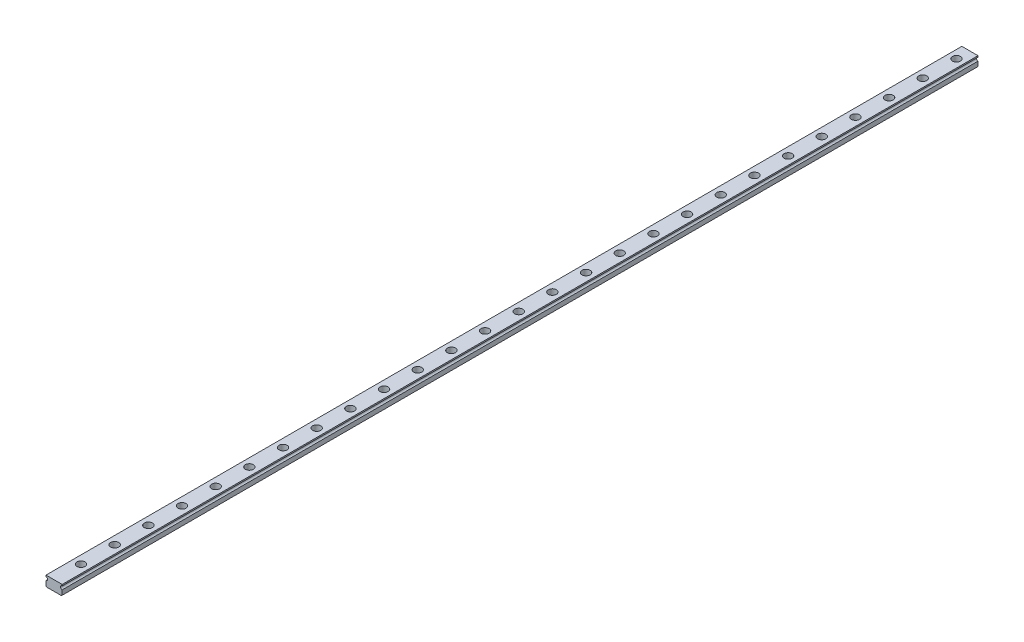
SolidWorks part; units mm, degrees
ref_plane "前视基准面" through (0, 0, 0) normal (0, 0, 1) x (1, 0, 0)
ref_plane "上视基准面" through (0, 0, 0) normal (0, 1, 0) x (1, 0, 0)
ref_plane "右视基准面" through (0, 0, 0) normal (1, 0, 0) x (0, 0, -1)
sketch "草图1" plane through (0, 0, 0) normal (0, 0, 1) x (1, 0, 0)
  line L0 (-6, 7.5) -> (-6, 6.5)
  line L1 (-6, 4) -> (-6, 0.5)
  line L2 (-6, 0.5) -> (-5.5, 0)
  line L3 (-5.5, 0) -> (5.5, 0)
  line L4 (5.5, 0) -> (6, 0.5)
  line L5 (6, 0.5) -> (6, 4)
  line L6 (6, 6.5) -> (6, 7.5)
  line L7 (6, 7.5) -> (-6, 7.5)
  arc A0 (-6, 6.5) -> (-6, 4) centre (-6, 5.25) cw
  arc A1 (6, 4) -> (6, 6.5) centre (6, 5.25) cw
extrude "凸台-拉伸1" add sketch "草图1" along normal blind 680
sketch "草图2" plane through (0, 0, 0) normal (1, 0, 0) x (0, 0, -1)
  line L0 (-10, 7.5) -> (-7, 7.5)
  line L1 (-7, 7.5) -> (-7, 3)
  line L2 (-7, 3) -> (-8.25, 3)
  line L3 (-8.25, 3) -> (-8.25, 0)
  line L4 (-8.25, 0) -> (-10, 0)
  line L5 (-10, 0) -> (-10, 7.5)
  line L6 (-10, 0) -> (-10, 7.5) construction
revolve "切除-旋转1" cut sketch "草图2" angle 360 about L6 reverse direction yes
ref_plane "基准面4" through (0, 7.5, 0) normal (0, 1, 0) x (1, 0, 0)
ref_plane "基准面5" through (0, 0, 0) normal (1, 0, 0) x (0, 0, -1)
ref_plane "基准面6" through (0, 0, 0) normal (1, 0, 0) x (0, 0, -1)
ref_plane "基准面7" through (0, 0, 0) normal (1, 0, 0) x (0, 0, -1)
ref_plane "基准面8" through (0, 0, 0) normal (1, 0, 0) x (0, 0, -1)
ref_plane "基准面9" through (0, 0, 0) normal (1, 0, 0) x (0, 0, -1)
ref_plane "基准面10" through (0, 0, 0) normal (1, 0, 0) x (0, 0, -1)
ref_plane "基准面11" through (0, 0, 0) normal (1, 0, 0) x (0, 0, -1)
ref_plane "基准面12" through (0, 0, 0) normal (1, 0, 0) x (0, 0, -1)
ref_plane "基准面13" through (0, 0, 0) normal (1, 0, 0) x (0, 0, -1)
ref_plane "基准面14" through (0, 0, 0) normal (1, 0, 0) x (0, 0, -1)
ref_plane "基准面15" through (0, 0, 0) normal (1, 0, 0) x (0, 0, -1)
ref_plane "基准面16" through (0, 0, 0) normal (1, 0, 0) x (0, 0, -1)
sketch "草图3" plane through (0, 0, 0) normal (1, 0, 0) x (0, 0, -1)
  line L0 (-310, 7.5) -> (-307, 7.5)
  line L1 (-307, 7.5) -> (-307, 3)
  line L2 (-307, 3) -> (-308.25, 3)
  line L3 (-308.25, 3) -> (-308.25, 0)
  line L4 (-308.25, 0) -> (-310, 0)
  line L5 (-310, 0) -> (-310, 7.5)
  line L6 (-310, 0) -> (-310, 7.5) construction
sketch "草图4" plane through (0, 0, 0) normal (1, 0, 0) x (0, 0, -1)
  line L0 (-285, 7.5) -> (-282, 7.5)
  line L1 (-282, 7.5) -> (-282, 3)
  line L2 (-282, 3) -> (-283.25, 3)
  line L3 (-283.25, 3) -> (-283.25, 0)
  line L4 (-283.25, 0) -> (-285, 0)
  line L5 (-285, 0) -> (-285, 7.5)
  line L6 (-285, 0) -> (-285, 7.5) construction
sketch "草图5" plane through (0, 0, 0) normal (1, 0, 0) x (0, 0, -1)
  line L0 (-260, 7.5) -> (-257, 7.5)
  line L1 (-257, 7.5) -> (-257, 3)
  line L2 (-257, 3) -> (-258.25, 3)
  line L3 (-258.25, 3) -> (-258.25, 0)
  line L4 (-258.25, 0) -> (-260, 0)
  line L5 (-260, 0) -> (-260, 7.5)
  line L6 (-260, 0) -> (-260, 7.5) construction
sketch "草图6" plane through (0, 0, 0) normal (1, 0, 0) x (0, 0, -1)
  line L0 (-235, 7.5) -> (-232, 7.5)
  line L1 (-232, 7.5) -> (-232, 3)
  line L2 (-232, 3) -> (-233.25, 3)
  line L3 (-233.25, 3) -> (-233.25, 0)
  line L4 (-233.25, 0) -> (-235, 0)
  line L5 (-235, 0) -> (-235, 7.5)
  line L6 (-235, 0) -> (-235, 7.5) construction
sketch "草图7" plane through (0, 0, 0) normal (1, 0, 0) x (0, 0, -1)
  line L0 (-210, 7.5) -> (-207, 7.5)
  line L1 (-207, 7.5) -> (-207, 3)
  line L2 (-207, 3) -> (-208.25, 3)
  line L3 (-208.25, 3) -> (-208.25, 0)
  line L4 (-208.25, 0) -> (-210, 0)
  line L5 (-210, 0) -> (-210, 7.5)
  line L6 (-210, 0) -> (-210, 7.5) construction
sketch "草图8" plane through (0, 0, 0) normal (1, 0, 0) x (0, 0, -1)
  line L0 (-185, 7.5) -> (-182, 7.5)
  line L1 (-182, 7.5) -> (-182, 3)
  line L2 (-182, 3) -> (-183.25, 3)
  line L3 (-183.25, 3) -> (-183.25, 0)
  line L4 (-183.25, 0) -> (-185, 0)
  line L5 (-185, 0) -> (-185, 7.5)
  line L6 (-185, 0) -> (-185, 7.5) construction
sketch "草图9" plane through (0, 0, 0) normal (1, 0, 0) x (0, 0, -1)
  line L0 (-160, 7.5) -> (-157, 7.5)
  line L1 (-157, 7.5) -> (-157, 3)
  line L2 (-157, 3) -> (-158.25, 3)
  line L3 (-158.25, 3) -> (-158.25, 0)
  line L4 (-158.25, 0) -> (-160, 0)
  line L5 (-160, 0) -> (-160, 7.5)
  line L6 (-160, 0) -> (-160, 7.5) construction
sketch "草图10" plane through (0, 0, 0) normal (1, 0, 0) x (0, 0, -1)
  line L0 (-135, 7.5) -> (-132, 7.5)
  line L1 (-132, 7.5) -> (-132, 3)
  line L2 (-132, 3) -> (-133.25, 3)
  line L3 (-133.25, 3) -> (-133.25, 0)
  line L4 (-133.25, 0) -> (-135, 0)
  line L5 (-135, 0) -> (-135, 7.5)
  line L6 (-135, 0) -> (-135, 7.5) construction
sketch "草图11" plane through (0, 0, 0) normal (1, 0, 0) x (0, 0, -1)
  line L0 (-110, 7.5) -> (-107, 7.5)
  line L1 (-107, 7.5) -> (-107, 3)
  line L2 (-107, 3) -> (-108.25, 3)
  line L3 (-108.25, 3) -> (-108.25, 0)
  line L4 (-108.25, 0) -> (-110, 0)
  line L5 (-110, 0) -> (-110, 7.5)
  line L6 (-110, 0) -> (-110, 7.5) construction
sketch "草图12" plane through (0, 0, 0) normal (1, 0, 0) x (0, 0, -1)
  line L0 (-85, 7.5) -> (-82, 7.5)
  line L1 (-82, 7.5) -> (-82, 3)
  line L2 (-82, 3) -> (-83.25, 3)
  line L3 (-83.25, 3) -> (-83.25, 0)
  line L4 (-83.25, 0) -> (-85, 0)
  line L5 (-85, 0) -> (-85, 7.5)
  line L6 (-85, 0) -> (-85, 7.5) construction
sketch "草图13" plane through (0, 0, 0) normal (1, 0, 0) x (0, 0, -1)
  line L0 (-60, 7.5) -> (-57, 7.5)
  line L1 (-57, 7.5) -> (-57, 3)
  line L2 (-57, 3) -> (-58.25, 3)
  line L3 (-58.25, 3) -> (-58.25, 0)
  line L4 (-58.25, 0) -> (-60, 0)
  line L5 (-60, 0) -> (-60, 7.5)
  line L6 (-60, 0) -> (-60, 7.5) construction
sketch "草图14" plane through (0, 0, 0) normal (1, 0, 0) x (0, 0, -1)
  line L0 (-35, 7.5) -> (-32, 7.5)
  line L1 (-32, 7.5) -> (-32, 3)
  line L2 (-32, 3) -> (-33.25, 3)
  line L3 (-33.25, 3) -> (-33.25, 0)
  line L4 (-33.25, 0) -> (-35, 0)
  line L5 (-35, 0) -> (-35, 7.5)
  line L6 (-35, 0) -> (-35, 7.5) construction
revolve "切除-旋转2" cut sketch "草图3" angle 360 about L6 reverse direction yes
revolve "切除-旋转3" cut sketch "草图4" angle 360 about L6 reverse direction yes
revolve "切除-旋转4" cut sketch "草图5" angle 360 about L6 reverse direction yes
revolve "切除-旋转5" cut sketch "草图6" angle 360 about L6 reverse direction yes
revolve "切除-旋转6" cut sketch "草图7" angle 360 about L6 reverse direction yes
revolve "切除-旋转7" cut sketch "草图8" angle 360 about L6 reverse direction yes
revolve "切除-旋转8" cut sketch "草图9" angle 360 about L6 reverse direction yes
revolve "切除-旋转9" cut sketch "草图10" angle 360 about L6 reverse direction yes
revolve "切除-旋转10" cut sketch "草图11" angle 360 about L6 reverse direction yes
revolve "切除-旋转11" cut sketch "草图12" angle 360 about L6 reverse direction yes
revolve "切除-旋转12" cut sketch "草图13" angle 360 about L6 reverse direction yes
revolve "切除-旋转13" cut sketch "草图14" angle 360 about L6 reverse direction yes
ref_plane "基准面17" through (0, 0, 160) normal (0, 0, 1) x (1, 0, 0)
ref_plane "基准面18" through (0, 0, 180.95) normal (0, 0, 1) x (1, 0, 0)
ref_plane "基准面19" through (0, 3, 0) normal (0, 1, 0) x (1, 0, 0)
ref_plane "to_block XY" through (0, 0, 160) normal (0, 0, 1) x (1, 0, 0)
ref_plane "to_block XZ" through (0, 7.5, 0) normal (0, -1, 0) x (-1, 0, 0)
ref_plane "to_block YZ" through (0, 0, 0) normal (1, 0, 0) x (0, 0, -1)
ref_axis "to_block X" through (-80.9, 7.5, 160) along (1, 0, 0)
ref_axis "to_block Y" through (0, -50, 160) along (0, 1, 0)
ref_axis "to_block Z" through (0, 7.5, 80.9) along (0, 0, -1)
sketch3d "to_block"
  point P0 (0, 7.5, 160)
ref_plane "to_block_2 XY" through (0, 0, 180.95) normal (0, 0, 1) x (1, 0, 0)
ref_plane "to_block_2 XZ" through (0, 7.5, 0) normal (0, -1, 0) x (-1, 0, 0)
ref_plane "to_block_2 YZ" through (0, 0, 0) normal (1, 0, 0) x (0, 0, -1)
ref_axis "to_block_2 X" through (-80.9, 7.5, 180.95) along (1, 0, 0)
ref_axis "to_block_2 Y" through (0, -50, 180.95) along (0, 1, 0)
ref_axis "to_block_2 Z" through (0, 7.5, 80.9) along (0, 0, -1)
sketch3d "to_block_2"
  point P0 (0, 7.5, 180.95)
ref_plane "to_kue XY" through (0, 0, 0) normal (0, 1, 0) x (1, 0, 0)
ref_plane "to_kue XZ" through (0, 0, 160) normal (0, 0, 1) x (1, 0, 0)
ref_plane "to_kue YZ" through (0, 0, 0) normal (1, 0, 0) x (0, 0, -1)
ref_axis "to_kue X" through (-80.9, 0, 160) along (1, 0, 0)
ref_axis "to_kue Y" through (0, 0, 50) along (0, 0, -1)
ref_axis "to_kue Z" through (0, 50, 160) along (0, -1, 0)
sketch3d "to_kue"
  point P0 (0, 0, 160)
ref_plane "rail_to bolt2 XY" through (0, 3, 0) normal (0, 1, 0) x (1, 0, 0)
ref_plane "rail_to bolt2 XZ" through (0, 0, 35) normal (0, 0, 1) x (1, 0, 0)
ref_plane "rail_to bolt2 YZ" through (0, 0, 0) normal (1, 0, 0) x (0, 0, -1)
ref_axis "rail_to bolt2 X" through (-80.9, 3, 35) along (1, 0, 0)
ref_axis "rail_to bolt2 Y" through (0, 3, 50) along (0, 0, -1)
ref_axis "rail_to bolt2 Z" through (0, 50, 35) along (0, -1, 0)
sketch3d "rail_to bolt2"
  point P0 (0, 3, 35)
ref_plane "rail_to_bolt7 XY" through (0, 3, 0) normal (0, 1, 0) x (1, 0, 0)
ref_plane "rail_to_bolt7 XZ" through (0, 0, 160) normal (0, 0, 1) x (1, 0, 0)
ref_plane "rail_to_bolt7 YZ" through (0, 0, 0) normal (1, 0, 0) x (0, 0, -1)
ref_axis "rail_to_bolt7 X" through (-80.9, 3, 160) along (1, 0, 0)
ref_axis "rail_to_bolt7 Y" through (0, 3, 50) along (0, 0, -1)
ref_axis "rail_to_bolt7 Z" through (0, 50, 160) along (0, -1, 0)
sketch3d "rail_to_bolt7"
  point P0 (0, 3, 160)
ref_plane "rail_to_bolt6 XY" through (0, 3, 0) normal (0, 1, 0) x (1, 0, 0)
ref_plane "rail_to_bolt6 XZ" through (0, 0, 135) normal (0, 0, 1) x (1, 0, 0)
ref_plane "rail_to_bolt6 YZ" through (0, 0, 0) normal (1, 0, 0) x (0, 0, -1)
ref_axis "rail_to_bolt6 X" through (-80.9, 3, 135) along (1, 0, 0)
ref_axis "rail_to_bolt6 Y" through (0, 3, 50) along (0, 0, -1)
ref_axis "rail_to_bolt6 Z" through (0, 50, 135) along (0, -1, 0)
sketch3d "rail_to_bolt6"
  point P0 (0, 3, 135)
ref_plane "rail_to_bolt5 XY" through (0, 3, 0) normal (0, 1, 0) x (1, 0, 0)
ref_plane "rail_to_bolt5 XZ" through (0, 0, 110) normal (0, 0, 1) x (1, 0, 0)
ref_plane "rail_to_bolt5 YZ" through (0, 0, 0) normal (1, 0, 0) x (0, 0, -1)
ref_axis "rail_to_bolt5 X" through (-80.9, 3, 110) along (1, 0, 0)
ref_axis "rail_to_bolt5 Y" through (0, 3, 50) along (0, 0, -1)
ref_axis "rail_to_bolt5 Z" through (0, 50, 110) along (0, -1, 0)
sketch3d "rail_to_bolt5"
  point P0 (0, 3, 110)
ref_plane "rail_to_bolt4 XY" through (0, 3, 0) normal (0, 1, 0) x (1, 0, 0)
ref_plane "rail_to_bolt4 XZ" through (0, 0, 85) normal (0, 0, 1) x (1, 0, 0)
ref_plane "rail_to_bolt4 YZ" through (0, 0, 0) normal (1, 0, 0) x (0, 0, -1)
ref_axis "rail_to_bolt4 X" through (-80.9, 3, 85) along (1, 0, 0)
ref_axis "rail_to_bolt4 Y" through (0, 3, 50) along (0, 0, -1)
ref_axis "rail_to_bolt4 Z" through (0, 50, 85) along (0, -1, 0)
sketch3d "rail_to_bolt4"
  point P0 (0, 3, 85)
ref_plane "rail_to_bolt3 XY" through (0, 3, 0) normal (0, 1, 0) x (1, 0, 0)
ref_plane "rail_to_bolt3 XZ" through (0, 0, 60) normal (0, 0, 1) x (1, 0, 0)
ref_plane "rail_to_bolt3 YZ" through (0, 0, 0) normal (1, 0, 0) x (0, 0, -1)
ref_axis "rail_to_bolt3 X" through (-80.9, 3, 60) along (1, 0, 0)
ref_axis "rail_to_bolt3 Y" through (0, 3, 50) along (0, 0, -1)
ref_axis "rail_to_bolt3 Z" through (0, 50, 60) along (0, -1, 0)
sketch3d "rail_to_bolt3"
  point P0 (0, 3, 60)
ref_plane "rail_to_bolt13 XY" through (0, 3, 0) normal (0, 1, 0) x (1, 0, 0)
ref_plane "rail_to_bolt13 XZ" through (0, 0, 310) normal (0, 0, 1) x (1, 0, 0)
ref_plane "rail_to_bolt13 YZ" through (0, 0, 0) normal (1, 0, 0) x (0, 0, -1)
ref_axis "rail_to_bolt13 X" through (-80.9, 3, 310) along (1, 0, 0)
ref_axis "rail_to_bolt13 Y" through (0, 3, 50) along (0, 0, -1)
ref_axis "rail_to_bolt13 Z" through (0, 50, 310) along (0, -1, 0)
sketch3d "rail_to_bolt13"
  point P0 (0, 3, 310)
ref_plane "rail_to_bolt12 XY" through (0, 3, 0) normal (0, 1, 0) x (1, 0, 0)
ref_plane "rail_to_bolt12 XZ" through (0, 0, 285) normal (0, 0, 1) x (1, 0, 0)
ref_plane "rail_to_bolt12 YZ" through (0, 0, 0) normal (1, 0, 0) x (0, 0, -1)
ref_axis "rail_to_bolt12 X" through (-80.9, 3, 285) along (1, 0, 0)
ref_axis "rail_to_bolt12 Y" through (0, 3, 50) along (0, 0, -1)
ref_axis "rail_to_bolt12 Z" through (0, 50, 285) along (0, -1, 0)
sketch3d "rail_to_bolt12"
  point P0 (0, 3, 285)
ref_plane "rail_to_bolt1 XY" through (0, 3, 0) normal (0, 1, 0) x (1, 0, 0)
ref_plane "rail_to_bolt1 XZ" through (0, 0, 10) normal (0, 0, 1) x (1, 0, 0)
ref_plane "rail_to_bolt1 YZ" through (0, 0, 0) normal (1, 0, 0) x (0, 0, -1)
ref_axis "rail_to_bolt1 X" through (-80.9, 3, 10) along (1, 0, 0)
ref_axis "rail_to_bolt1 Y" through (0, 3, 50) along (0, 0, -1)
ref_axis "rail_to_bolt1 Z" through (0, 50, 10) along (0, -1, 0)
sketch3d "rail_to_bolt1"
  point P0 (0, 3, 10)
ref_plane "rail_to_bolt11 XY" through (0, 3, 0) normal (0, 1, 0) x (1, 0, 0)
ref_plane "rail_to_bolt11 XZ" through (0, 0, 260) normal (0, 0, 1) x (1, 0, 0)
ref_plane "rail_to_bolt11 YZ" through (0.178, 0, 0) normal (1, 0, 0) x (0, 0, -1)
ref_axis "rail_to_bolt11 X" through (-80.9, 3, 260) along (1, 0, 0)
ref_axis "rail_to_bolt11 Y" through (0.178, 3, 50) along (0, 0, -1)
ref_axis "rail_to_bolt11 Z" through (0.178, 50, 260) along (0, -1, 0)
sketch3d "rail_to_bolt11"
  point P0 (0.178, 3, 260)
ref_plane "rail_to_bolt10 XY" through (0, 3, 0) normal (0, 1, 0) x (1, 0, 0)
ref_plane "rail_to_bolt10 XZ" through (0, 0, 235) normal (0, 0, 1) x (1, 0, 0)
ref_plane "rail_to_bolt10 YZ" through (0, 0, 0) normal (1, 0, 0) x (0, 0, -1)
ref_axis "rail_to_bolt10 X" through (-80.9, 3, 235) along (1, 0, 0)
ref_axis "rail_to_bolt10 Y" through (0, 3, 50) along (0, 0, -1)
ref_axis "rail_to_bolt10 Z" through (0, 50, 235) along (0, -1, 0)
sketch3d "rail_to_bolt10"
  point P0 (0, 3, 235)
ref_plane "rail_to_bolt9 XY" through (0, 3, 0) normal (0, 1, 0) x (1, 0, 0)
ref_plane "rail_to_bolt9 XZ" through (0, 0, 210) normal (0, 0, 1) x (1, 0, 0)
ref_plane "rail_to_bolt9 YZ" through (0, 0, 0) normal (1, 0, 0) x (0, 0, -1)
ref_axis "rail_to_bolt9 X" through (-80.9, 3, 210) along (1, 0, 0)
ref_axis "rail_to_bolt9 Y" through (0, 3, 50) along (0, 0, -1)
ref_axis "rail_to_bolt9 Z" through (0, 50, 210) along (0, -1, 0)
sketch3d "rail_to_bolt9"
  point P0 (0, 3, 210)
ref_plane "rail_to_bolt8 XY" through (0, 3, 0) normal (0, 1, 0) x (1, 0, 0)
ref_plane "rail_to_bolt8 XZ" through (0, 0, 185) normal (0, 0, 1) x (1, 0, 0)
ref_plane "rail_to_bolt8 YZ" through (0, 0, 0) normal (1, 0, 0) x (0, 0, -1)
ref_axis "rail_to_bolt8 X" through (-80.9, 3, 185) along (1, 0, 0)
ref_axis "rail_to_bolt8 Y" through (0, 3, 50) along (0, 0, -1)
ref_axis "rail_to_bolt8 Z" through (0, 50, 185) along (0, -1, 0)
sketch3d "rail_to_bolt8"
  point P0 (0, 3, 185)
ref_plane "rail_to_bolt 7 XY" through (0, 3, 0) normal (0, 1, 0) x (1, 0, 0)
ref_plane "rail_to_bolt 7 XZ" through (0, 0, 160) normal (0, 0, 1) x (1, 0, 0)
ref_plane "rail_to_bolt 7 YZ" through (0, 0, 0) normal (1, 0, 0) x (0, 0, -1)
ref_axis "rail_to_bolt 7 X" through (-80.9, 3, 160) along (1, 0, 0)
ref_axis "rail_to_bolt 7 Y" through (0, 3, 50) along (0, 0, -1)
ref_axis "rail_to_bolt 7 Z" through (0, 50, 160) along (0, -1, 0)
sketch3d "rail_to_bolt 7"
  point P0 (0, 3, 160)
ref_plane "rail_to_bolt 6 XY" through (0, 3, 0) normal (0, 1, 0) x (1, 0, 0)
ref_plane "rail_to_bolt 6 XZ" through (0, 0, 135) normal (0, 0, 1) x (1, 0, 0)
ref_plane "rail_to_bolt 6 YZ" through (0, 0, 0) normal (1, 0, 0) x (0, 0, -1)
ref_axis "rail_to_bolt 6 X" through (-80.9, 3, 135) along (1, 0, 0)
ref_axis "rail_to_bolt 6 Y" through (0, 3, 50) along (0, 0, -1)
ref_axis "rail_to_bolt 6 Z" through (0, 50, 135) along (0, -1, 0)
sketch3d "rail_to_bolt 6"
  point P0 (0, 3, 135)
ref_plane "rail_to_bolt 5 XY" through (0, 3, 0) normal (0, 1, 0) x (1, 0, 0)
ref_plane "rail_to_bolt 5 XZ" through (0, 0, 110) normal (0, 0, 1) x (1, 0, 0)
ref_plane "rail_to_bolt 5 YZ" through (0, 0, 0) normal (1, 0, 0) x (0, 0, -1)
ref_axis "rail_to_bolt 5 X" through (-80.9, 3, 110) along (1, 0, 0)
ref_axis "rail_to_bolt 5 Y" through (0, 3, 50) along (0, 0, -1)
ref_axis "rail_to_bolt 5 Z" through (0, 50, 110) along (0, -1, 0)
sketch3d "rail_to_bolt 5"
  point P0 (0, 3, 110)
ref_plane "rail_to_bolt 4 XY" through (0, 3, 0) normal (0, 1, 0) x (1, 0, 0)
ref_plane "rail_to_bolt 4 XZ" through (0, 0, 85) normal (0, 0, 1) x (1, 0, 0)
ref_plane "rail_to_bolt 4 YZ" through (0, 0, 0) normal (1, 0, 0) x (0, 0, -1)
ref_axis "rail_to_bolt 4 X" through (-80.9, 3, 85) along (1, 0, 0)
ref_axis "rail_to_bolt 4 Y" through (0, 3, 50) along (0, 0, -1)
ref_axis "rail_to_bolt 4 Z" through (0, 50, 85) along (0, -1, 0)
sketch3d "rail_to_bolt 4"
  point P0 (0, 3, 85)
ref_plane "rail_to_bolt 3 XY" through (0, 3, 0) normal (0, 1, 0) x (1, 0, 0)
ref_plane "rail_to_bolt 3 XZ" through (0, 0, 60) normal (0, 0, 1) x (1, 0, 0)
ref_plane "rail_to_bolt 3 YZ" through (0, 0, 0) normal (1, 0, 0) x (0, 0, -1)
ref_axis "rail_to_bolt 3 X" through (-80.9, 3, 60) along (1, 0, 0)
ref_axis "rail_to_bolt 3 Y" through (0, 3, 50) along (0, 0, -1)
ref_axis "rail_to_bolt 3 Z" through (0, 50, 60) along (0, -1, 0)
sketch3d "rail_to_bolt 3"
  point P0 (0, 3, 60)
ref_plane "rail_to_bolt 13 XY" through (0, 3, 0) normal (0, 1, 0) x (1, 0, 0)
ref_plane "rail_to_bolt 13 XZ" through (0, 0, 310) normal (0, 0, 1) x (1, 0, 0)
ref_plane "rail_to_bolt 13 YZ" through (0, 0, 0) normal (1, 0, 0) x (0, 0, -1)
ref_axis "rail_to_bolt 13 X" through (-80.9, 3, 310) along (1, 0, 0)
ref_axis "rail_to_bolt 13 Y" through (0, 3, 50) along (0, 0, -1)
ref_axis "rail_to_bolt 13 Z" through (0, 50, 310) along (0, -1, 0)
sketch3d "rail_to_bolt 13"
  point P0 (0, 3, 310)
ref_plane "rail_to_bolt 2 XY" through (0, 3, 0) normal (0, 1, 0) x (1, 0, 0)
ref_plane "rail_to_bolt 2 XZ" through (0, 0, 35) normal (0, 0, 1) x (1, 0, 0)
ref_plane "rail_to_bolt 2 YZ" through (0, 0, 0) normal (1, 0, 0) x (0, 0, -1)
ref_axis "rail_to_bolt 2 X" through (-80.9, 3, 35) along (1, 0, 0)
ref_axis "rail_to_bolt 2 Y" through (0, 3, 50) along (0, 0, -1)
ref_axis "rail_to_bolt 2 Z" through (0, 50, 35) along (0, -1, 0)
sketch3d "rail_to_bolt 2"
  point P0 (0, 3, 35)
ref_plane "rail_to_bolt 12 XY" through (0, 3, 0) normal (0, 1, 0) x (1, 0, 0)
ref_plane "rail_to_bolt 12 XZ" through (0, 0, 285) normal (0, 0, 1) x (1, 0, 0)
ref_plane "rail_to_bolt 12 YZ" through (0, 0, 0) normal (1, 0, 0) x (0, 0, -1)
ref_axis "rail_to_bolt 12 X" through (-80.9, 3, 285) along (1, 0, 0)
ref_axis "rail_to_bolt 12 Y" through (0, 3, 50) along (0, 0, -1)
ref_axis "rail_to_bolt 12 Z" through (0, 50, 285) along (0, -1, 0)
sketch3d "rail_to_bolt 12"
  point P0 (0, 3, 285)
ref_plane "rail_to_bolt 1 XY" through (0, 3, 0) normal (0, 1, 0) x (1, 0, 0)
ref_plane "rail_to_bolt 1 XZ" through (0, 0, 10) normal (0, 0, 1) x (1, 0, 0)
ref_plane "rail_to_bolt 1 YZ" through (0, 0, 0) normal (1, 0, 0) x (0, 0, -1)
ref_axis "rail_to_bolt 1 X" through (-80.9, 3, 10) along (1, 0, 0)
ref_axis "rail_to_bolt 1 Y" through (0, 3, 50) along (0, 0, -1)
ref_axis "rail_to_bolt 1 Z" through (0, 50, 10) along (0, -1, 0)
sketch3d "rail_to_bolt 1"
  point P0 (0, 3, 10)
ref_plane "rail_to_bolt 11 XY" through (0, 3, 0) normal (0, 1, 0) x (1, 0, 0)
ref_plane "rail_to_bolt 11 XZ" through (0, 0, 260) normal (0, 0, 1) x (1, 0, 0)
ref_plane "rail_to_bolt 11 YZ" through (0, 0, 0) normal (1, 0, 0) x (0, 0, -1)
ref_axis "rail_to_bolt 11 X" through (-80.9, 3, 260) along (1, 0, 0)
ref_axis "rail_to_bolt 11 Y" through (0, 3, 50) along (0, 0, -1)
ref_axis "rail_to_bolt 11 Z" through (0, 50, 260) along (0, -1, 0)
sketch3d "rail_to_bolt 11"
  point P0 (0, 3, 260)
ref_plane "rail_to_bolt 10 XY" through (0, 3, 0) normal (0, 1, 0) x (1, 0, 0)
ref_plane "rail_to_bolt 10 XZ" through (0, 0, 235) normal (0, 0, 1) x (1, 0, 0)
ref_plane "rail_to_bolt 10 YZ" through (0, 0, 0) normal (1, 0, 0) x (0, 0, -1)
ref_axis "rail_to_bolt 10 X" through (-80.9, 3, 235) along (1, 0, 0)
ref_axis "rail_to_bolt 10 Y" through (0, 3, 50) along (0, 0, -1)
ref_axis "rail_to_bolt 10 Z" through (0, 50, 235) along (0, -1, 0)
sketch3d "rail_to_bolt 10"
  point P0 (0, 3, 235)
ref_plane "rail_to_bolt 9 XY" through (0, 3, 0) normal (0, 1, 0) x (1, 0, 0)
ref_plane "rail_to_bolt 9 XZ" through (0, 0, 210) normal (0, 0, 1) x (1, 0, 0)
ref_plane "rail_to_bolt 9 YZ" through (0, 0, 0) normal (1, 0, 0) x (0, 0, -1)
ref_axis "rail_to_bolt 9 X" through (-80.9, 3, 210) along (1, 0, 0)
ref_axis "rail_to_bolt 9 Y" through (0, 3, 50) along (0, 0, -1)
ref_axis "rail_to_bolt 9 Z" through (0, 50, 210) along (0, -1, 0)
sketch3d "rail_to_bolt 9"
  point P0 (0, 3, 210)
ref_plane "rail_to_bolt 8 XY" through (0, 3, 0) normal (0, 1, 0) x (1, 0, 0)
ref_plane "rail_to_bolt 8 XZ" through (0, 0, 185) normal (0, 0, 1) x (1, 0, 0)
ref_plane "rail_to_bolt 8 YZ" through (0, 0, 0) normal (1, 0, 0) x (0, 0, -1)
ref_axis "rail_to_bolt 8 X" through (-80.9, 3, 185) along (1, 0, 0)
ref_axis "rail_to_bolt 8 Y" through (0, 3, 50) along (0, 0, -1)
ref_axis "rail_to_bolt 8 Z" through (0, 50, 185) along (0, -1, 0)
sketch3d "rail_to_bolt 8"
  point P0 (0, 3, 185)
ref_plane "rail_to_adjusting_block XY" through (0, 0, 0) normal (0, 1, 0) x (1, 0, 0)
ref_plane "rail_to_adjusting_block XZ" through (0, 0, 10) normal (0, 0, 1) x (1, 0, 0)
ref_plane "rail_to_adjusting_block YZ" through (0, 0, 0) normal (1, 0, 0) x (0, 0, -1)
ref_axis "rail_to_adjusting_block X" through (-80.9, 0, 10) along (1, 0, 0)
ref_axis "rail_to_adjusting_block Y" through (0, 0, 50) along (0, 0, -1)
ref_axis "rail_to_adjusting_block Z" through (0, 50, 10) along (0, -1, 0)
sketch3d "rail_to_adjusting_block"
  point P0 (0, 0, 10)
pattern_linear "阵列(线性)1" count 15 spacing 25 along (0, 0, 1) of "切除-旋转2"
